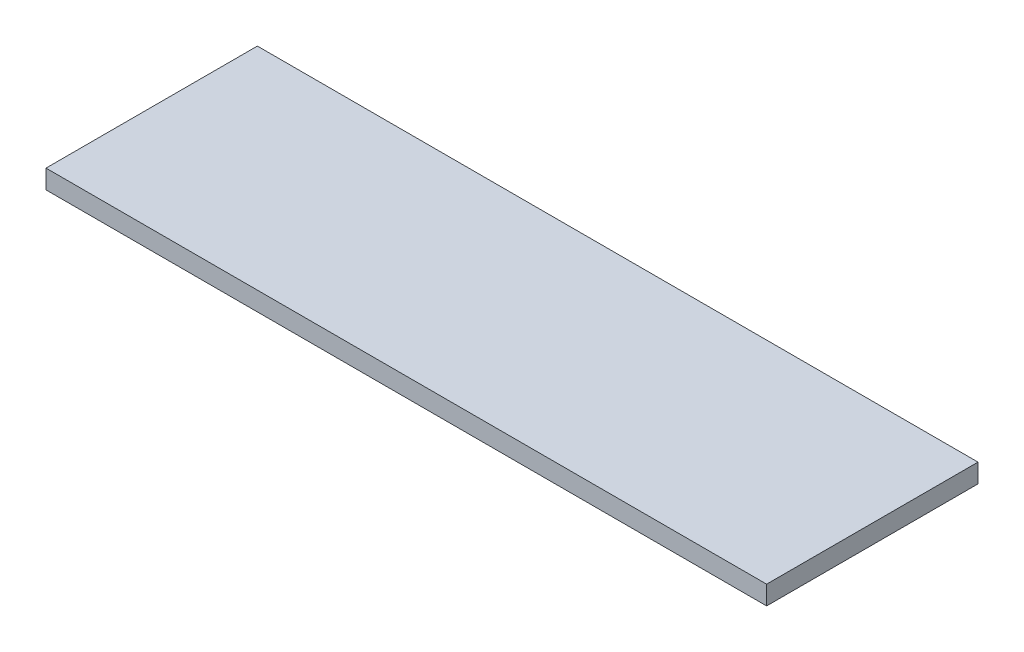
SolidWorks part; units mm, degrees
ref_plane "Front" through (0, 0, 0) normal (0, 0, 1) x (1, 0, 0)
ref_plane "Top" through (0, 0, 0) normal (0, 1, 0) x (1, 0, 0)
ref_plane "Right" through (0, 0, 0) normal (1, 0, 0) x (0, 0, -1)
sketch "Sketch1" plane through (0, 0, 0) normal (0, 1, 0) x (1, 0, 0)
  line L1 (0, 0) -> (242.4, 0)
  line L2 (0, 0) -> (0, 71.1)
  line L3 (0, 71.1) -> (242.4, 71.1)
  line L4 (242.4, 0) -> (242.4, 71.1)
  dimension "D1" = 71.1
  dimension "D2" = 242.4
extrude "Boss-Extrude1" add sketch "Sketch1" along normal blind 6.35
